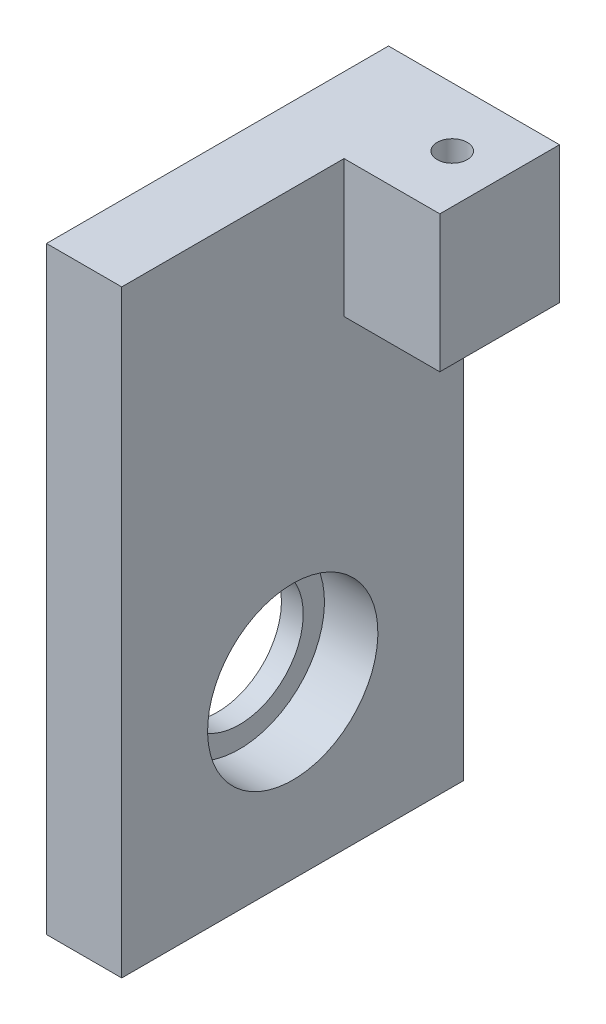
SolidWorks part; units mm, degrees
ref_plane "Front Plane" through (0, 0, 0) normal (0, 0, 1) x (1, 0, 0)
ref_plane "Top Plane" through (0, 0, 0) normal (0, 1, 0) x (1, 0, 0)
ref_plane "Right Plane" through (0, 0, 0) normal (1, 0, 0) x (0, 0, -1)
sketch "Sketch1" plane through (0, 0, -3.1935) normal (0, 0, 1) x (1, 0, 0)
  line L1 (-8.7255, -32.4424) -> (-3.1375, -32.4424)
  line L2 (-8.7255, -32.4424) -> (-8.7255, 12.0076)
  line L3 (-8.7255, 12.0076) -> (-3.1375, 12.0076)
  line L4 (-3.1375, -32.4424) -> (-3.1375, 12.0076)
  dimension "D1" = 5.588
  dimension "D2" = 44.45
extrude "Boss-Extrude1" add sketch "Sketch1" along normal blind 25.4
sketch "Sketch2" plane through (-3.1375, 0, 0) normal (1, 0, 0) x (0, 0, -1)
  line L1 (3.1935, 12.0076) -> (-5.6965, 12.0076)
  line L2 (3.1935, 12.0076) -> (3.1935, 1.8476)
  line L3 (3.1935, 1.8476) -> (-5.6965, 1.8476)
  line L4 (-5.6965, 12.0076) -> (-5.6965, 1.8476)
  dimension "D1" = 10.16
  dimension "D2" = 8.89
extrude "Boss-Extrude2" add sketch "Sketch2" along normal blind 7.112
sketch "Sketch3" plane through (-3.1375, 0, 0) normal (1, 0, 0) x (0, 0, -1)
  circle A0 centre (-9.5065, -19.7424) radius 6.35 construction
  circle A1 centre (-9.5065, -19.7424) radius 6.35
  circle A2 centre (-9.5065, -19.7424) radius 6.3246
  dimension "D1" = 0.0254
sketch "Sketch4" plane through (-3.1375, 0, 0) normal (1, 0, 0) x (0, 0, -1)
  circle A0 centre (-9.5065, -19.7424) radius 4.7494 construction
  circle A1 centre (-9.5065, -19.7424) radius 4.7494
extrude "Cut-Extrude1" cut sketch "Sketch4" against normal up to surface (5.588 mm away) up to face at (-8.7255, -10.2174, 9.5065)
extrude "Cut-Extrude2" cut sketch "Sketch3" against normal up to surface (3.9688 mm away) contours A2 region at (-3.1375, -19.7424, 9.5065)
sketch "Sketch5" plane through (0, 12.0076, 0) normal (0, 1, 0) x (1, 0, 0)
  circle A0 centre (0.3931, -1.193) radius 0.9906 construction
  circle A1 centre (0.3931, -1.193) radius 0.9906
  circle A2 centre (0.3931, -1.193) radius 1.1176
  dimension "D1" = 0.127
extrude "Cut-Extrude3" cut sketch "Sketch5" against normal up to surface (10.16 mm away) contours A1 | A2 A1 region at (0.3931, 12.0076, 1.193) region at (-0.6929, 12.0076, 1.193) up to face at (1.3075, 1.8476, 2.3627)
